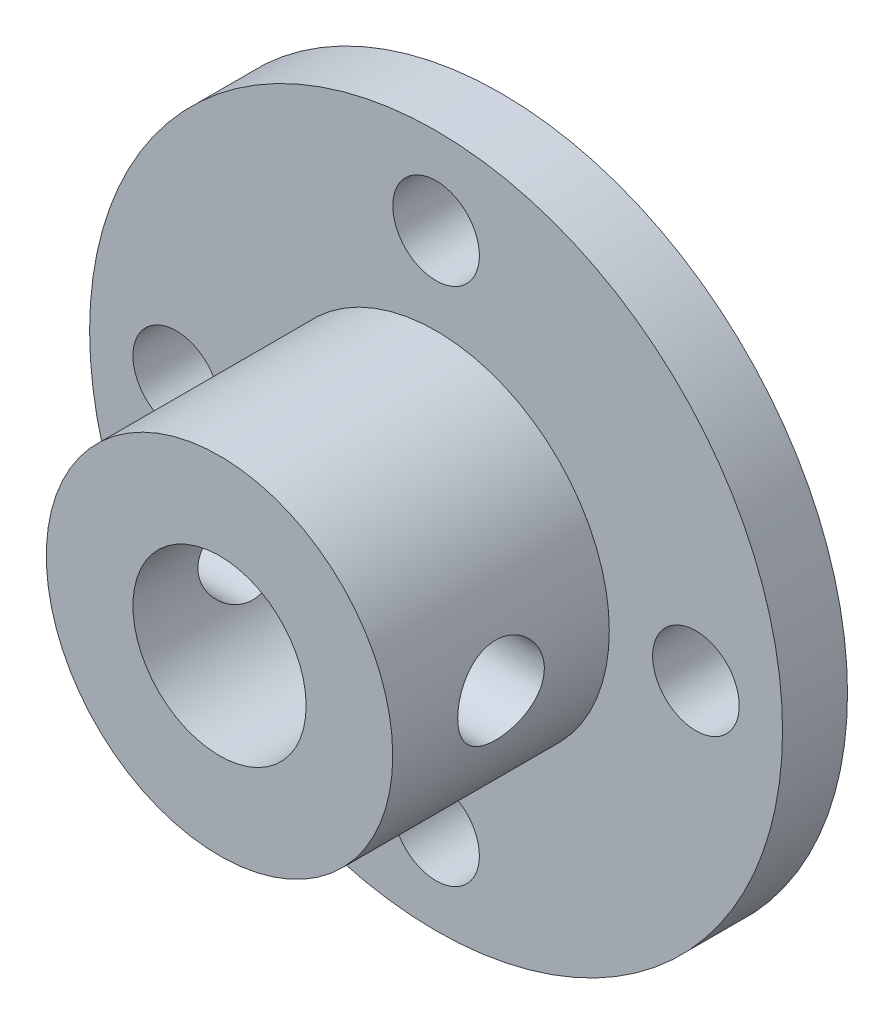
SolidWorks part; units mm, degrees
ref_plane "Front Plane" through (0, 0, 0) normal (1, 0, 0) x (0, 1, 0)
ref_plane "Top Plane" through (0, 0, 0) normal (0, 0, 1) x (0, 1, 0)
ref_plane "Right Plane" through (0, 0, 0) normal (0, 1, 0) x (-1, 0, 0)
sketch "Sketch1" plane through (0, 0, 0) normal (0, 0, 1) x (0, 1, 0)
  circle A0 centre (0, 0) radius 4
  circle A1 centre (0, 0) radius 8
  circle A2 centre (0, 0) radius 16
  circle A3 centre (0, 0) radius 12 construction
  circle A4 centre (0, 12) radius 2
  circle A5 centre (12, 0) radius 2
  circle A6 centre (0, -12) radius 2
  circle A7 centre (-12, 0) radius 2
  point P17 (0, 0)
  dimension "D1" = 8
  dimension "D2" = 16
  dimension "D3" = 32
  dimension "D4" = 24
  dimension "D5" = 4
  dimension "D6" = 4
extrude "Boss-Extrude1" add sketch "Sketch1" along normal blind 3 contours A2 A7 A6 A5 A4 A1 region at (0, -15.5475, 0)
extrude "Boss-Extrude2" add sketch "Sketch1<3>" along normal blind 13 contours A1 A0 region at (0, -7.7737, 0)
sketch "Sketch1<3>" plane through (0, 0, 0) normal (0, 0, 1) x (0, 1, 0) same geometry as "Sketch1"
sketch "Sketch2" plane through (0, 0, 0) normal (1, 0, 0) x (0, 1, 0)
  line L2 (0, 0) -> (0, 3) construction
  line L3 (16, 3) -> (-16, 3) construction
  line L4 (0, 3) -> (0, 13) construction
  line L5 (8, 13) -> (-8, 13) construction
  circle A0 centre (0, 8) radius 2
  dimension "D1" = 4
extrude "Cut-Extrude1" cut sketch "Sketch2" against normal through all both and the other way through all
